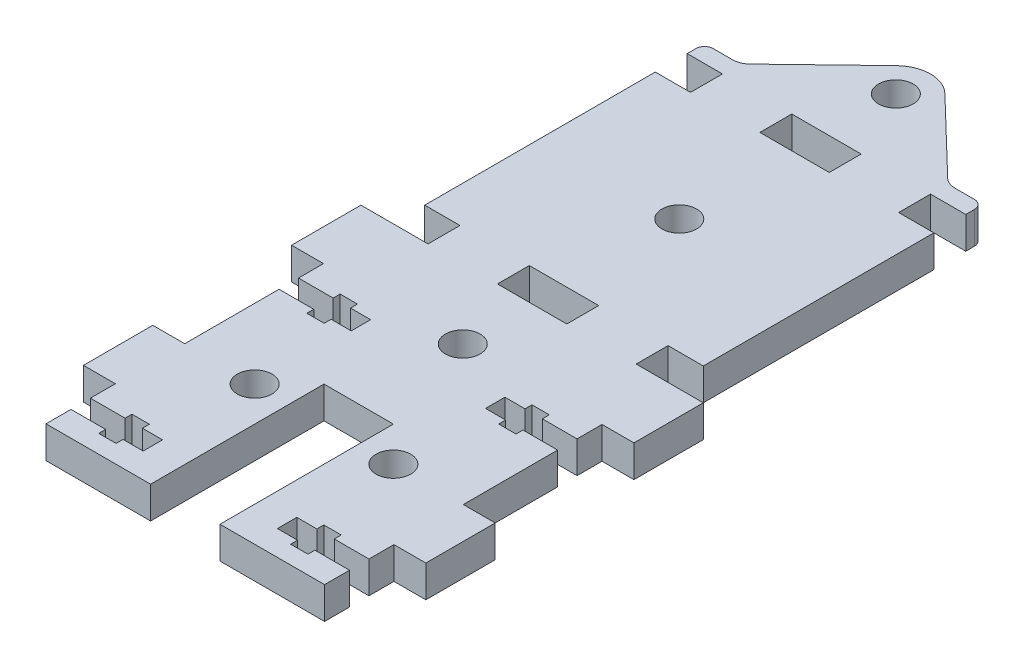
SolidWorks part; units mm, degrees
ref_plane "Front Plane" through (0, 0, 0) normal (0, 0, 1) x (1, 0, 0)
ref_plane "Top Plane" through (0, 0, 0) normal (0, 1, 0) x (1, 0, 0)
ref_plane "Right Plane" through (0, 0, 0) normal (1, 0, 0) x (0, 0, -1)
sketch "Sketch1" plane through (0, 0, 0) normal (0, 1, 0) x (1, 0, 0)
  line L0 (19.05, 24.0268) -> (6.35, 24.0268) construction
  line L1 (25.5, -21.1058) -> (19.05, -21.1058)
  line L2 (25.5, -21.1058) -> (25.5, 21.1058)
  line L3 (25.5, 21.1058) -> (19.05, 21.1058)
  line L4 (-25.5, -21.1058) -> (-25.5, 21.1058)
  line L5 (0, 21.1058) -> (0, -21.1058) construction
  line L6 (25.5, 0) -> (-25.5, 0) construction
  line L7 (-19.05, 26.9478) -> (-25.5, 26.9478)
  line L8 (-19.05, 26.9478) -> (-19.05, 21.1058)
  line L9 (25.5, 21.1058) -> (25.5, 26.9478) construction
  line L10 (-6.35, 26.9478) -> (-6.35, 21.1058)
  line L11 (-12.7, 21.1058) -> (-12.7, 26.9478) construction
  line L12 (-19.05, 24.0268) -> (-6.35, 24.0268) construction
  line L13 (12.7, 21.1058) -> (12.7, 26.9478) construction
  line L14 (6.35, 26.9478) -> (6.35, 21.1058)
  line L15 (-19.05, 21.1058) -> (-25.5, 21.1058)
  line L16 (19.05, 26.9478) -> (19.05, 21.1058)
  line L17 (0, -21.1058) -> (0, -65.0478) construction
  line L18 (12.7, -21.1058) -> (12.7, -26.9478) construction
  line L19 (-19.05, -24.0268) -> (-6.35, -24.0268) construction
  line L20 (-12.7, -21.1058) -> (-12.7, -26.9478) construction
  line L21 (19.05, -24.0268) -> (6.35, -24.0268) construction
  line L22 (31.342, -33.2978) -> (25.5, -33.2978) construction
  line L23 (19.05, -26.9478) -> (19.05, -21.1058)
  line L24 (6.35, 21.1058) -> (-6.35, 21.1058)
  line L25 (6.35, -26.9478) -> (6.35, -21.1058)
  line L26 (-6.35, -26.9478) -> (-6.35, -21.1058)
  line L27 (6.35, -21.1058) -> (-6.35, -21.1058)
  line L28 (-19.05, -26.9478) -> (-19.05, -21.1058)
  line L29 (6.35, -26.9478) -> (-6.35, -26.9478)
  line L30 (-19.05, -21.1058) -> (-25.5, -21.1058)
  line L31 (25.5, 30.1228) -> (-25.5, 30.1228)
  line L32 (25.5, 30.1228) -> (25.5, 26.9478)
  line L33 (25.5, 26.9478) -> (19.05, 26.9478)
  line L34 (-25.5, 30.1228) -> (-25.5, 26.9478)
  line L35 (0, 26.9478) -> (0, 30.1228) construction
  line L36 (25.5, 28.5353) -> (-25.5, 28.5353) construction
  line L37 (6.35, 26.9478) -> (-6.35, 26.9478)
  line L38 (-19.05, -26.9478) -> (-25.5, -26.9478)
  line L39 (-25.5, -39.6478) -> (-25.5, -65.0478)
  line L40 (-31.342, -77.7478) -> (-25.5, -77.7478)
  line L41 (25.5, -26.9478) -> (19.05, -26.9478)
  line L42 (-31.342, -77.7478) -> (-31.342, -65.0478)
  line L43 (0, -26.9478) -> (0, -103.1478) construction
  line L44 (25.5, -65.0478) -> (-25.5, -65.0478) construction
  line L45 (-31.342, -39.6478) -> (-25.5, -39.6478)
  line L46 (-31.342, -39.6478) -> (-31.342, -26.9478)
  line L47 (-31.342, -26.9478) -> (-25.5, -26.9478)
  line L48 (28.421, -26.9478) -> (28.421, -39.6478) construction
  line L49 (-28.421, -26.9478) -> (-28.421, -39.6478) construction
  line L50 (-31.342, -33.2978) -> (-25.5, -33.2978) construction
  line L51 (31.342, -26.9478) -> (25.5, -26.9478)
  line L52 (31.342, -39.6478) -> (31.342, -26.9478)
  line L53 (31.342, -39.6478) -> (25.5, -39.6478)
  line L54 (-31.342, -65.0478) -> (-25.5, -65.0478)
  line L55 (-25.5, -77.7478) -> (-25.5, -90.4478)
  line L56 (25.5, -39.6478) -> (25.5, -65.0478)
  line L57 (25.5, -77.7478) -> (25.5, -90.4478)
  line L58 (31.342, -65.0478) -> (25.5, -65.0478)
  line L59 (31.342, -77.7478) -> (31.342, -65.0478)
  line L60 (31.342, -77.7478) -> (25.5, -77.7478)
  line L61 (-31.342, -71.3978) -> (31.342, -71.3978) construction
  line L62 (6.35, -90.4478) -> (26.8151, -90.4478)
  line L63 (-25.5, -90.4478) -> (-6.35, -90.4478)
  line L64 (6.35, -84.0978) -> (-6.35, -84.0978)
  line L65 (6.35, -84.0978) -> (6.35, -90.4478)
  line L67 (-6.35, -84.0978) -> (-6.35, -90.4478)
  line L68 (6.35, -84.0978) -> (-6.35, -90.4478) construction
  line L69 (6.35, -90.4478) -> (-6.35, -84.0978) construction
  circle A0 centre (-12.7, -71.3978) radius 3.175 construction
  circle A1 centre (12.7, -71.3978) radius 3.175 construction
  point P0 (0, 0)
  point P4 (-12.7, 24.0268)
  point P16 (12.7, 24.0268)
  point P39 (12.7, -24.0268)
  point P40 (-12.7, -24.0268)
  point P41 (0, 28.5353)
  point P49 (-28.421, -33.2978)
  point P59 (28.421, -33.2978)
  point P74 (0, -87.2728)
  dimension "D12" = 12.7
  dimension "D1" = 51
  dimension "D2" = 42.2116
  dimension "D3" = 5.842
  dimension "D4" = 12.7
  dimension "D5" = 12.7
  dimension "D6" = 3.175
  dimension "D7" = 51
  dimension "D8" = 63.5
  dimension "D9" = 12.7
  dimension "D10" = 5.842
  dimension "D13" = 6.35
  dimension "D11" = 2
extrude "Boss-Extrude1" add sketch "Sketch1" along normal blind 5.842 contours L53 L52 L51 L41 L23 L1 L2 L3 L16 L33 L32 L31 L34 L7 L8 L15 L4 L30 L28 L38 L47 L46 L45 L40 L59 L25 L29 L26 L27 L37 L14 L24 region at (0, 0, 31.9759)
fillet "Fillet1" radius 1.5875 2 edges at (25.5, 2.921, -30.1228) (-25.5, 2.921, -30.1228)
sketch "Sketch2" plane through (0, 5.842, 0) normal (0, 1, 0) x (1, 0, 0)
  line L0 (-25.5, -45.9978) -> (25.5, -45.9978) construction
  line L1 (-25.5, -39.6478) -> (-25.5, -65.0478) construction
  line L2 (25.5, -39.6478) -> (25.5, -65.0478) construction
  line L3 (-31.342, -39.6478) -> (-25.5, -39.6478) construction
  line L4 (-19.15, -44.2198) -> (-19.15, -42.9498)
  line L5 (-19.15, -47.7758) -> (-25.5, -47.7758)
  line L6 (-15.975, -44.2198) -> (-15.975, -42.9498)
  line L7 (-19.15, -44.2198) -> (-25.5, -44.2198)
  line L8 (-25.5, -47.7758) -> (-25.5, -44.2198)
  line L9 (-19.15, -47.7758) -> (-25.5, -44.2198) construction
  line L10 (-19.15, -44.2198) -> (-25.5, -47.7758) construction
  line L11 (-15.975, -49.0458) -> (-19.15, -49.0458)
  line L12 (-15.975, -49.0458) -> (-15.975, -47.7758)
  line L13 (-15.975, -42.9498) -> (-19.15, -42.9498)
  line L14 (-19.15, -49.0458) -> (-19.15, -47.7758)
  line L15 (-15.975, -49.0458) -> (-19.15, -42.9498) construction
  line L16 (-15.975, -42.9498) -> (-19.15, -49.0458) construction
  line L17 (-12.292, -47.7758) -> (-15.975, -47.7758)
  line L18 (-12.292, -47.7758) -> (-12.292, -44.2198)
  line L19 (-12.292, -44.2198) -> (-15.975, -44.2198)
  line L20 (0, -26.9478) -> (0, -84.0978) construction
  line L21 (-12.292, -47.7758) -> (-15.975, -44.2198) construction
  line L22 (-12.292, -44.2198) -> (-15.975, -47.7758) construction
  line L23 (6.35, -26.9478) -> (-6.35, -26.9478) construction
  line L24 (6.35, -84.0978) -> (-6.35, -84.0978) construction
  line L25 (12.292, -44.2198) -> (15.975, -47.7758) construction
  line L26 (12.292, -47.7758) -> (15.975, -44.2198) construction
  line L27 (15.975, -42.9498) -> (19.15, -49.0458) construction
  line L28 (15.975, -49.0458) -> (19.15, -42.9498) construction
  line L29 (19.15, -44.2198) -> (25.5, -47.7758) construction
  line L30 (19.15, -47.7758) -> (25.5, -44.2198) construction
  line L31 (12.292, -44.2198) -> (15.975, -44.2198)
  line L32 (12.292, -47.7758) -> (12.292, -44.2198)
  line L33 (12.292, -47.7758) -> (15.975, -47.7758)
  line L34 (19.15, -49.0458) -> (19.15, -47.7758)
  line L35 (15.975, -42.9498) -> (19.15, -42.9498)
  line L36 (15.975, -49.0458) -> (15.975, -47.7758)
  line L37 (15.975, -49.0458) -> (19.15, -49.0458)
  line L38 (25.5, -47.7758) -> (25.5, -44.2198)
  line L39 (19.15, -44.2198) -> (25.5, -44.2198)
  line L40 (15.975, -44.2198) -> (15.975, -42.9498)
  line L41 (19.15, -47.7758) -> (25.5, -47.7758)
  line L42 (19.15, -44.2198) -> (19.15, -42.9498)
  line L43 (-25.5, -65.0478) -> (25.5, -65.0478) construction
  line L46 (19.15, -82.3198) -> (25.5, -85.8758) construction
  line L47 (19.15, -85.8758) -> (25.5, -82.3198) construction
  line L48 (15.975, -81.0498) -> (19.15, -87.1458) construction
  line L49 (15.975, -87.1458) -> (19.15, -81.0498) construction
  line L50 (12.292, -82.3198) -> (15.975, -85.8758) construction
  line L51 (12.292, -85.8758) -> (15.975, -82.3198) construction
  line L52 (-12.292, -85.8758) -> (-15.975, -82.3198) construction
  line L53 (-12.292, -82.3198) -> (-15.975, -85.8758) construction
  line L54 (-15.975, -87.1458) -> (-19.15, -81.0498) construction
  line L55 (-15.975, -81.0498) -> (-19.15, -87.1458) construction
  line L56 (-19.15, -85.8758) -> (-25.5, -82.3198) construction
  line L57 (-19.15, -82.3198) -> (-25.5, -85.8758) construction
  line L58 (-25.5, -84.0978) -> (25.5, -84.0978) construction
  line L59 (19.15, -85.8758) -> (19.15, -87.1458)
  line L60 (19.15, -82.3198) -> (25.5, -82.3198)
  line L61 (15.975, -85.8758) -> (15.975, -87.1458)
  line L62 (19.15, -85.8758) -> (25.5, -85.8758)
  line L63 (25.5, -82.3198) -> (25.5, -85.8758)
  line L64 (15.975, -81.0498) -> (19.15, -81.0498)
  line L65 (15.975, -81.0498) -> (15.975, -82.3198)
  line L66 (15.975, -87.1458) -> (19.15, -87.1458)
  line L67 (19.15, -81.0498) -> (19.15, -82.3198)
  line L68 (12.292, -82.3198) -> (15.975, -82.3198)
  line L69 (12.292, -82.3198) -> (12.292, -85.8758)
  line L70 (12.292, -85.8758) -> (15.975, -85.8758)
  line L71 (-12.292, -85.8758) -> (-15.975, -85.8758)
  line L72 (-12.292, -82.3198) -> (-12.292, -85.8758)
  line L73 (-12.292, -82.3198) -> (-15.975, -82.3198)
  line L74 (-19.15, -81.0498) -> (-19.15, -82.3198)
  line L75 (-15.975, -87.1458) -> (-19.15, -87.1458)
  line L76 (-15.975, -81.0498) -> (-15.975, -82.3198)
  line L77 (-15.975, -81.0498) -> (-19.15, -81.0498)
  line L78 (-25.5, -82.3198) -> (-25.5, -85.8758)
  line L79 (-19.15, -85.8758) -> (-25.5, -85.8758)
  line L80 (-15.975, -85.8758) -> (-15.975, -87.1458)
  line L81 (-19.15, -82.3198) -> (-25.5, -82.3198)
  line L82 (-19.15, -85.8758) -> (-19.15, -87.1458)
  point P8 (-22.325, -45.9978)
  point P13 (-17.5625, -45.9978)
  point P18 (-14.1335, -45.9978)
  point P41 (14.1335, -45.9978)
  point P42 (17.5625, -45.9978)
  point P43 (22.325, -45.9978)
  point P72 (22.325, -84.0978)
  point P73 (17.5625, -84.0978)
  point P74 (14.1335, -84.0978)
  point P75 (-14.1335, -84.0978)
  point P76 (-17.5625, -84.0978)
  point P77 (-22.325, -84.0978)
  dimension "D1" = 6.35
  dimension "D2" = 3.556
  dimension "D3" = 6.35
  dimension "D4" = 3.175
  dimension "D5" = 6.096
  dimension "D6" = 3.556
  dimension "D7" = 3.683
  dimension "D8" = 19.05
extrude "Cut-Extrude1" cut sketch "Sketch2" against normal through all
sketch "Sketch3" plane through (0, 5.842, 0) normal (0, 1, 0) x (1, 0, 0)
  line L0 (0, 30.1228) -> (0, -84.0978) construction
  line L1 (23.9125, 30.1228) -> (-23.9125, 30.1228) construction
  line L2 (6.35, -84.0978) -> (-6.35, -84.0978) construction
  line L3 (-25.5, -65.0478) -> (25.5, -65.0478) construction
  circle A0 centre (0, 0) radius 3.175
  circle A1 centre (-12.7, -65.0478) radius 3.175
  circle A2 centre (12.7, -65.0478) radius 3.175
  circle A3 centre (0, -39.6478) radius 3.175
  dimension "D1" = 6.35
  dimension "D2" = 6.35
  dimension "D4" = 6.35
  dimension "D3" = 12.7
  dimension "D5" = 25.4
extrude "Cut-Extrude2" cut sketch "Sketch3" against normal through all
sketch "Sketch4" plane through (0, 5.842, 0) normal (0, 1, 0) x (1, 0, 0)
  line L0 (0, 21.1058) -> (0, 39.6478) construction
  line L1 (6.35, 21.1058) -> (-6.35, 21.1058) construction
  line L2 (23.9125, 30.1228) -> (-23.9125, 30.1228) construction
  line L3 (-19.05, 30.1228) -> (-4.404, 44.2224)
  line L4 (19.05, 30.1228) -> (4.404, 44.2224)
  line L5 (-19.05, 30.1228) -> (19.05, 30.1228)
  circle A0 centre (0, 39.6478) radius 3.175
  arc A1 (4.404, 44.2224) -> (-4.404, 44.2224) centre (0, 39.6478) ccw
  circle A3 centre (0, 39.6478) radius 6.35 construction
  point P14 (6.35, 39.6478)
  dimension "D2" = 6.35
  dimension "D1" = 9.525
  dimension "D3" = 3.175
extrude "Boss-Extrude2" add sketch "Sketch4" against normal up to surface (5.842 mm away) up to face at (0, 0, 42.8228)
fillet "Fillet2" radius 3.175 2 edges at (19.05, 2.921, -30.1228) (-19.05, 2.921, -30.1228)
sketch "Sketch5" plane through (0, 5.842, 0) normal (0, 1, 0) x (1, 0, 0)
  line L1 (6.35, -58.6978) -> (-6.35, -58.6978)
  line L2 (6.35, -58.6978) -> (6.35, -84.0978)
  line L3 (6.35, -84.0978) -> (-6.35, -84.0978)
  line L4 (-6.35, -58.6978) -> (-6.35, -84.0978)
  line L5 (6.35, -58.6978) -> (-6.35, -84.0978) construction
  line L6 (6.35, -84.0978) -> (-6.35, -58.6978) construction
  point P0 (0, -71.3978)
  dimension "D1" = 25.4
extrude "Cut-Extrude3" cut sketch "Sketch5" against normal through all
